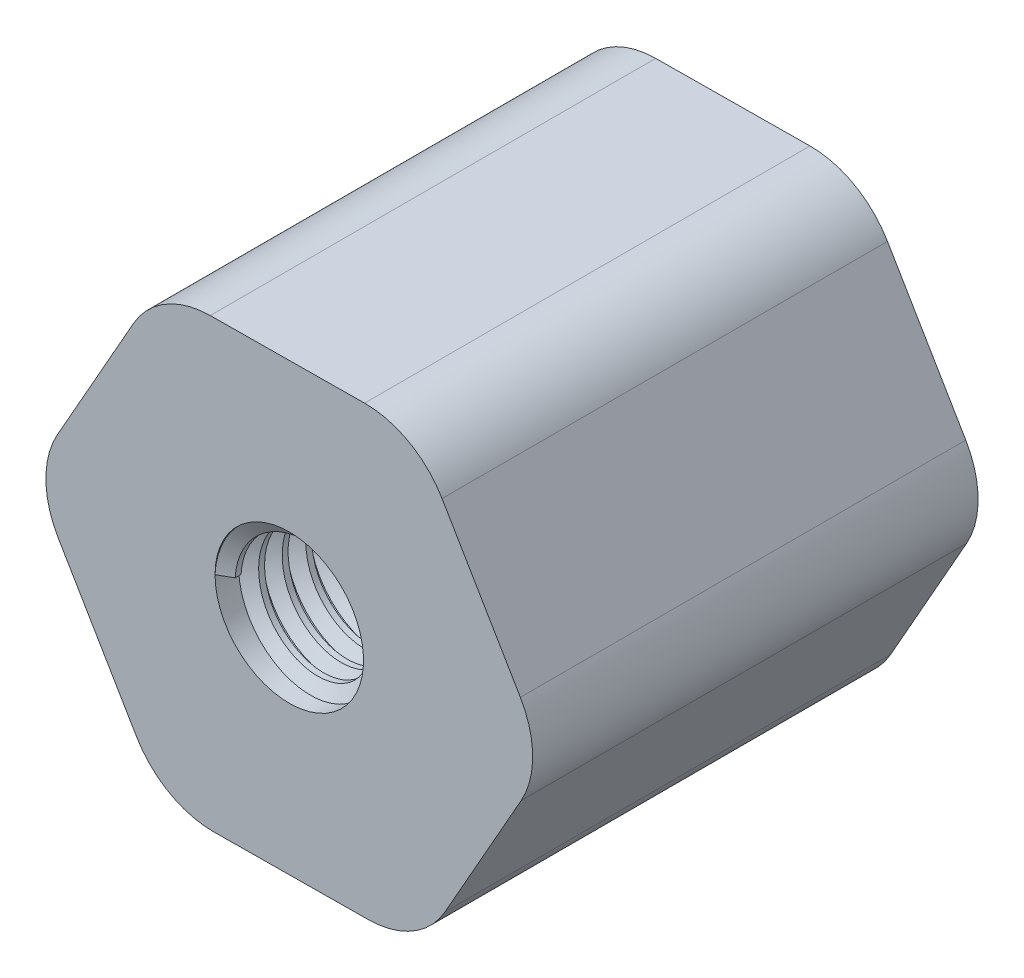
SolidWorks part; units mm, degrees
ref_plane "Alzado" through (0, 0, 0) normal (0, 0, 1) x (1, 0, 0)
ref_plane "Planta" through (0, 0, 0) normal (0, 1, 0) x (1, 0, 0)
ref_plane "Vista lateral" through (0, 0, 0) normal (1, 0, 0) x (0, 0, -1)
sketch "Croquis1" plane through (0, 0, 0) normal (0, 0, 1) x (1, 0, 0)
  line L1 (2.5343, 7.5218) -> (-2.6617, 7.4777)
  line L2 (-5.2469, 5.9556) -> (-7.8067, 1.4337)
  line L3 (-7.7812, -1.5662) -> (-5.145, -6.0439)
  line L4 (-2.5343, -7.5218) -> (2.6617, -7.4777)
  line L5 (5.2469, -5.9556) -> (7.8067, -1.4337)
  line L6 (7.7812, 1.5662) -> (5.145, 6.0439)
  circle A0 centre (0, 0) radius 2.5
  circle A1 centre (0, 0) radius 7.5 construction
  arc A2 (-2.6617, 7.4777) -> (-5.2469, 5.9556) centre (-2.6362, 4.4778) ccw
  arc A3 (2.5343, 7.5218) -> (5.145, 6.0439) centre (2.5598, 4.5219) cw
  arc A4 (7.8067, -1.4337) -> (7.7812, 1.5662) centre (5.196, 0.0441) ccw
  arc A5 (2.6617, -7.4777) -> (5.2469, -5.9556) centre (2.6362, -4.4778) ccw
  arc A6 (-5.145, -6.0439) -> (-2.5343, -7.5218) centre (-2.5598, -4.5219) ccw
  arc A7 (-7.8067, 1.4337) -> (-7.7812, -1.5662) centre (-5.196, -0.0441) ccw
  dimension "D1" = 15
  dimension "D2" = 5
  dimension "D3" = 3
extrude "Saliente-Extruir1" add sketch "Croquis1" along normal blind 15
thread "Rosca1" pitch 0.7937 method extrude profile "Perfil de rosca2" start angle 0, offset 0, length 14.3, pitch 0.7937, diameter 5
ref_plane "Plano2" through (-2.5, 0, 15) normal (0, -1, 0) x (-1, 0, 0)
sketch "Perfil de rosca2" plane through (-2.5, 0, 15) normal (0, -1, 0) x (-1, 0, 0)
  line L0 (0, 0) -> (0, 0.7937) construction
  line L11 (0, 0) -> (0, 0.6945)
  line L12 (0, 0.6945) -> (-0.4296, 0.4465)
  line L13 (-0.4296, 0.4465) -> (-0.4296, 0.248)
  line L15 (-0.4296, 0.248) -> (0, 0)
  line L17 (-0.4296, 0.3473) -> (0, 0.3473) construction
  point P2 (0, 0)
  dimension "Pitch" = 0.7937
  dimension "Profile_Angle" = 60
  dimension "Profile_Land" = 0.1984
  dimension "Profile_Height" = 0.4296
